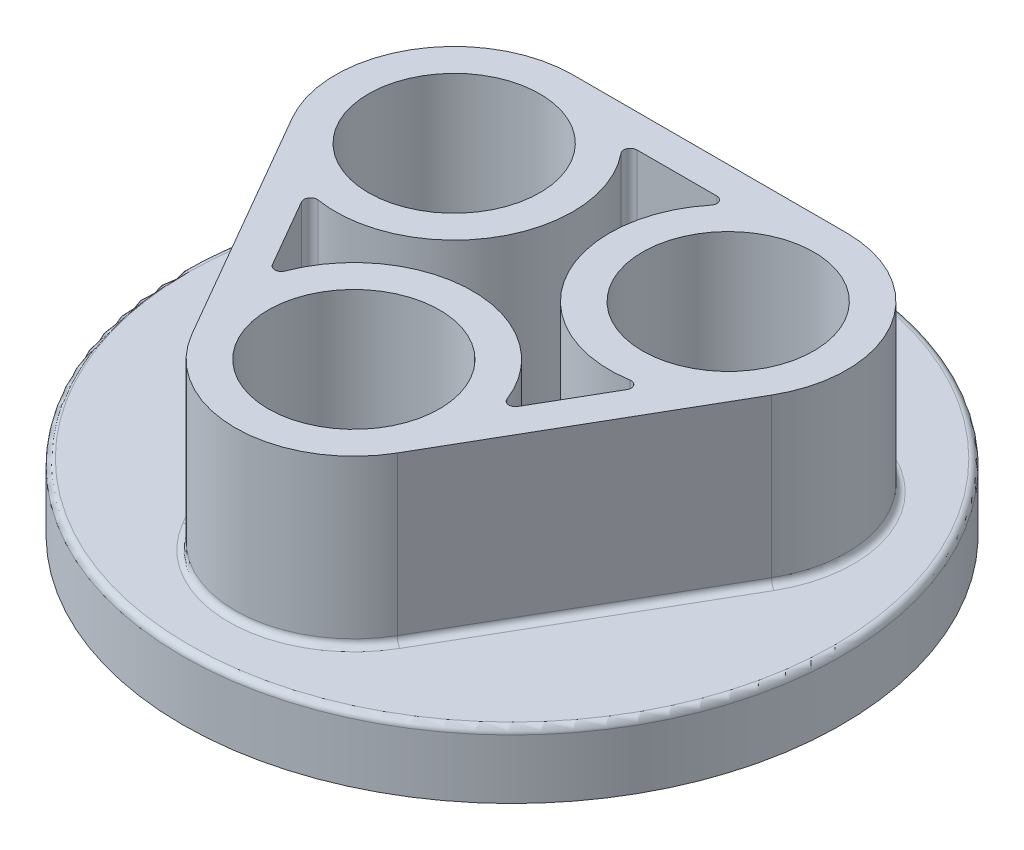
SolidWorks part; units mm, degrees
ref_plane "Front Plane" through (0, 0, 0) normal (0, 0, 1) x (1, 0, 0)
ref_plane "Top Plane" through (0, 0, 0) normal (0, 1, 0) x (1, 0, 0)
ref_plane "Right Plane" through (0, 0, 0) normal (1, 0, 0) x (0, 0, -1)
sketch "Sketch1" plane through (0, 0, 0) normal (0, 1, 0) x (1, 0, 0)
  line L0 (-36.3731, 3) -> (-15.5885, -33)
  line L1 (-20.7846, 30) -> (20.7846, 30)
  line L2 (36.3731, 3) -> (15.5885, -33)
  line L3 (-25.818, -5.2819) -> (-17.4833, -19.7181)
  line L4 (-8.3347, 25) -> (8.3347, 25)
  line L5 (25.818, -5.2819) -> (17.4833, -19.7181)
  circle A0 centre (0, 0) radius 50
  circle A1 centre (0, 0) radius 24 construction
  circle A2 centre (0, -24) radius 13
  circle A3 centre (0, -24) radius 18
  circle A4 centre (-20.7846, 12) radius 18
  circle A5 centre (-20.7846, 12) radius 13
  circle A6 centre (20.7846, 12) radius 18
  circle A7 centre (20.7846, 12) radius 13
  circle A8 centre (0, 0) radius 45
  point P16 (0, 0)
  point P22 (-21.6506, -12.5)
  dimension "D1" = 100
  dimension "D2" = 48
  dimension "D3" = 26
  dimension "D4" = 36
  dimension "D9" = 5
  dimension "D6" = 5
  dimension "D7" = 5
  dimension "D8" = 5
  dimension "D5" = 3
extrude "Boss-Extrude6" add sketch "Sketch1" against normal blind 10 contours A0 A8 | A4 A5 | A3 A2 | A6 A7 region at (-35.9322, 0, -20.7454) region at (-17.3156, 0, 26.4703) region at (33.1525, 0, -24.3679) region at (-48.5858, 0, 0)
extrude "Boss-Extrude8" add sketch "Sketch1<7>" against normal blind 5 contours A8 A6 L2 A3 L0 A4 L1 | A4 L0 A3 L3 | A6 L5 A3 L2 | A6 L1 A4 L4 | A6 L4 A4 L3 A3 L5 region at (-24.1033, 0, 13.916) region at (0, 0, -27.8321) region at (0, 0, 0) region at (24.1033, 0, 13.916) region at (-43.7272, 0, 0)
sketch "Sketch1<7>" plane through (0, 0, 0) normal (0, 1, 0) x (1, 0, 0) same geometry as "Sketch1"
extrude "Boss-Extrude9" add sketch "Sketch1<8>" along normal blind 25 contours A3 A2 | A4 L0 A3 L3 | A4 A5 | A6 L1 A4 L4 | A6 A7 | A6 L5 A3 L2 region at (-24.1033, 0, 13.916) region at (-35.9322, 0, -20.7454) region at (-17.3156, 0, 26.4703) region at (0, 0, -27.8321) region at (24.1033, 0, 13.916) region at (33.1525, 0, -24.3679)
sketch "Sketch1<8>" plane through (0, 0, 0) normal (0, 1, 0) x (1, 0, 0) same geometry as "Sketch1"
fillet "Fillet1" radius 1 20 edges at (0, -5, 45) (0, 0, 50) (-20.7846, -5, 6) (0, -5, 42) (20.7846, -5, 6) (-8.3347, 12.5, -25) (8.3347, 12.5, -25) (25.818, 12.5, 5.2819) (17.4833, 12.5, 19.7181) (-17.4833, 12.5, 19.7181) (-25.818, 12.5, 5.2819) (-21.6506, 0, 12.5) (0, 0, 6) (21.6506, 0, 12.5) (0, 0, -25) (-5.1962, 0, -3) (5.1962, 0, -3) (25.9808, 0, 15) (-25.9808, 0, 15) (0, 0, -30)
